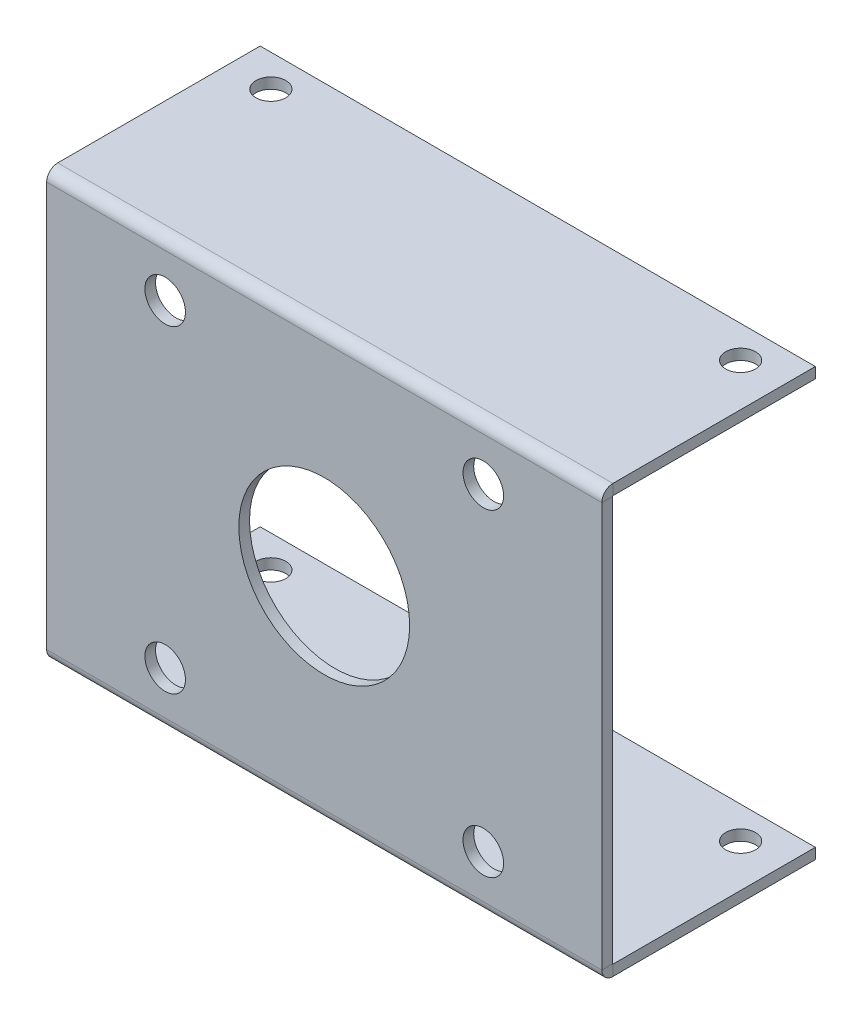
SolidWorks part; units mm, degrees
note: The reader was unsure of these and kept them because the rebuilt part matched: flange length of "Edge-Flange1", "Edge-Flange2".
material "ASTM A36 Steel"
ref_plane "Front Plane" through (0, 0, 0) normal (0, 0, 1) x (1, 0, 0)
ref_plane "Top Plane" through (0, 0, 0) normal (0, 1, 0) x (1, 0, 0)
ref_plane "Right Plane" through (0, 0, 0) normal (1, 0, 0) x (0, 0, -1)
sketch "Sketch1" plane through (0, 0, 0) normal (0, 0, 1) x (1, 0, 0)
  line L1 (-130, -100) -> (130, -100)
  line L2 (-130, -100) -> (-130, 100)
  line L3 (-130, 100) -> (130, 100)
  line L4 (130, -100) -> (130, 100)
  line L5 (-130, -100) -> (130, 100) construction
  line L6 (-130, 100) -> (130, -100) construction
  point P0 (0, 0)
  dimension "D1" = 260
  dimension "D2" = 200
base flange "Base-Flange1" sketch "Sketch1" thickness 5 reverse thickness direction no parameters "D1"=0.2
edge flange "Edge-Flange1" sketch "Sketch8" flange angle 90 flange length 100 flange position material inside bend radius 0.2 thickness 5 relief rectangular parameters "D6"=10
sketch "Sketch8" plane through (0, 100, -5) normal (0, -1, 0) x (-1, 0, 0)
  line L2 (-130, 0) -> (-130, 95)
  line L3 (-130, 95) -> (130, 95)
  line L4 (130, 95) -> (130, 0)
  line L9 (130, 0) -> (-130, 0) construction
  line L10 (130, 0) -> (-130, 0)
bend "EdgeBend1" bend radius 0.2 bend angle 90 parameters "D5"=1
edge flange "Edge-Flange2" sketch "Sketch11" flange angle 90 flange length 100 flange position material inside bend radius 0.2 thickness 5 relief rectangular parameters "D6"=10
sketch "Sketch11" plane through (0, -100, -5) normal (0, -1, 0) x (-1, 0, 0)
  line L2 (-130, 0) -> (-130, 95)
  line L3 (-130, 95) -> (130, 95)
  line L4 (130, 95) -> (130, 0)
  line L7 (130, 0) -> (-130, 0) construction
  line L8 (130, 0) -> (-130, 0)
bend "EdgeBend2" bend radius 0.2 bend angle 90 parameters "D5"=2
sketch "Sketch12" plane through (0, 0, 0) normal (0, 0, 1) x (1, 0, 0)
  circle A0 centre (0, 0) radius 40
  dimension "D1" = 80
extrude "Cut-Extrude1" cut sketch "Sketch12" against normal through all both and the other way through all normal cut yes
sketch "Sketch13" plane through (0, 0, 0) normal (0, 0, 1) x (1, 0, 0)
  line L1 (-130, -100) -> (130, -100) construction
  circle A0 centre (74.5, 74.5) radius 9.5
  circle A1 centre (-74.5, 74.5) radius 9.5
  circle A2 centre (-74.5, -74.5) radius 9.5
  circle A3 centre (74.5, -74.5) radius 9.5
  circle A6 centre (0, 0) radius 40 construction
  point P0 (0, 0)
  dimension "D3" = 19
  dimension "D4" = 19
  dimension "D5" = 19
  dimension "D6" = 19
  dimension "D7" = 149
  dimension "D8" = 74.5
  dimension "D9" = 25.5
  dimension "D10" = 25.5
  dimension "D11" = 0
  dimension "D12" = 0
  dimension "D1" = 149
  dimension "D2" = 149
extrude "Cut-Extrude2" cut sketch "Sketch13" against normal through all both and the other way through all normal cut yes
sketch "Sketch14" plane through (0, -100, 0) normal (0, -1, 0) x (-1, 0, 0)
  line L0 (-130, 100) -> (-130, 5.2) construction
  line L1 (130, 5.2) -> (130, 100) construction
  line L2 (130, 100) -> (-130, 100) construction
  circle A0 centre (110, 85) radius 7
  circle A1 centre (-110, 85) radius 7
  dimension "D1" = 14
  dimension "D2" = 14
  dimension "D3" = 20
  dimension "D4" = 20
  dimension "D5" = 15
  dimension "D6" = 15
extrude "Cut-Extrude3" cut sketch "Sketch14" against normal through all both and the other way through all normal cut yes
sketch "Bend-Lines1" [suppressed] plane through (0, 0, 0) normal (0, 1, 0) x (1, 0, 0)
sketch "Bounding-Box1" [suppressed] plane through (0, 0, 0) normal (0, 1, 0) x (1, 0, 0)
sheet metal parameters "Sheet-Metal1" thickness 5 parameters "D1"=0.2
flat pattern "Flat-Pattern1" [suppressed]
sketch "Bend-Lines2" plane through (0, 0, 0) normal (0, 1, 0) x (1, 0, 0)
sketch3d "Bounding-Box2" [suppressed]
  line L0 (-85, 100, 0) -> (-85, -100, 0) construction
  line L1 (85, 100, 0) -> (85, -100, 0) construction
  line L2 (-85, 100, 0) -> (85, 100, 0) construction
  line L3 (-85, -100, 0) -> (85, -100, 0) construction
sheet metal parameters "Sheet-Metal2" thickness 5 parameters "D1"=0.2
flat pattern "Flat-Pattern1"
sketch "Bend-Lines2" plane through (0, 0, 0) normal (0, 0, 1) x (1, 0, 0)
  line L0 (85, 96.9206) -> (-85, 96.9206) construction
  line L1 (85, 96.9206) -> (-85, 96.9206) construction
sketch3d "Bounding-Box2" [suppressed]
  line L0 (85, 143.8412, 0) -> (85, -100, 0) construction
  line L1 (-85, 143.8412, 0) -> (-85, -100, 0) construction
  line L2 (85, 143.8412, 0) -> (-85, 143.8412, 0) construction
  line L3 (85, -100, 0) -> (-85, -100, 0) construction
bend of the flat pattern "Flatten-<EdgeBend1>1"
sheet metal parameters "Sheet-Metal3" thickness 5 parameters "D1"=0.2
flat pattern "Flat-Pattern1"
sketch "Bend-Lines2" plane through (0, 0, 0) normal (0, 0, 1) x (1, 0, 0)
  line L0 (85, 96.9206) -> (-85, 96.9206) construction
  line L1 (85, 96.9206) -> (-85, 96.9206) construction
  line L2 (-85, -96.9206) -> (85, -96.9206) construction
  line L3 (-85, -96.9206) -> (85, -96.9206) construction
sketch3d "Bounding-Box2" [suppressed]
  line L0 (85, 143.8412, 0) -> (85, -143.8412, 0) construction
  line L1 (-85, 143.8412, 0) -> (-85, -143.8412, 0) construction
  line L2 (85, 143.8412, 0) -> (-85, 143.8412, 0) construction
  line L3 (85, -143.8412, 0) -> (-85, -143.8412, 0) construction
bend of the flat pattern "Flatten-<EdgeBend1>1"
bend of the flat pattern "Flatten-<EdgeBend2>1"
sheet metal parameters "Sheet-Metal4" thickness 5 parameters "D1"=0.2
flat pattern "Flat-Pattern1"
sketch "Bend-Lines2" plane through (0, 0, 0) normal (0, 0, 1) x (1, 0, 0)
  line L0 (85, 96.9206) -> (-85, 96.9206) construction
  line L1 (85, 96.9206) -> (-85, 96.9206) construction
  line L2 (-85, -96.9206) -> (85, -96.9206) construction
  line L3 (-85, -96.9206) -> (85, -96.9206) construction
sketch3d "Bounding-Box2" [suppressed]
  line L0 (85, 143.8412, 0) -> (85, -143.8412, 0) construction
  line L1 (-85, 143.8412, 0) -> (-85, -143.8412, 0) construction
  line L2 (85, 143.8412, 0) -> (-85, 143.8412, 0) construction
  line L3 (85, -143.8412, 0) -> (-85, -143.8412, 0) construction
bend of the flat pattern "Flatten-<EdgeBend1>1"
bend of the flat pattern "Flatten-<EdgeBend2>1"
sheet metal parameters "Sheet-Metal5" thickness 5 parameters "D1"=0.2
flat pattern "Flat-Pattern1"
sketch "Bend-Lines2" plane through (0, 0, 0) normal (0, 0, 1) x (1, 0, 0)
  line L0 (85, 96.9206) -> (-85, 96.9206) construction
  line L1 (85, 96.9206) -> (-85, 96.9206) construction
  line L2 (-85, -96.9206) -> (85, -96.9206) construction
  line L3 (-85, -96.9206) -> (85, -96.9206) construction
sketch3d "Bounding-Box2" [suppressed]
  line L0 (85, 143.8412, 0) -> (85, -143.8412, 0) construction
  line L1 (-85, 143.8412, 0) -> (-85, -143.8412, 0) construction
  line L2 (85, 143.8412, 0) -> (-85, 143.8412, 0) construction
  line L3 (85, -143.8412, 0) -> (-85, -143.8412, 0) construction
bend of the flat pattern "Flatten-<EdgeBend1>1"
bend of the flat pattern "Flatten-<EdgeBend2>1"
sheet metal parameters "Sheet-Metal6" thickness 5 parameters "D1"=0.2
flat pattern "Flat-Pattern1"
sketch "Bend-Lines2" plane through (0, 0, 0) normal (0, 0, 1) x (1, 0, 0)
  line L0 (130, 96.9206) -> (-130, 96.9206) construction
  line L1 (130, 96.9206) -> (-130, 96.9206) construction
  line L2 (-130, -96.9206) -> (130, -96.9206) construction
  line L3 (-130, -96.9206) -> (130, -96.9206) construction
sketch3d "Bounding-Box2" [suppressed]
  line L0 (130, 193.8412, 0) -> (130, -193.8412, 0) construction
  line L1 (-130, 193.8412, 0) -> (-130, -193.8412, 0) construction
  line L2 (130, 193.8412, 0) -> (-130, 193.8412, 0) construction
  line L3 (130, -193.8412, 0) -> (-130, -193.8412, 0) construction
bend of the flat pattern "Flatten-<EdgeBend1>1"
bend of the flat pattern "Flatten-<EdgeBend2>1"
